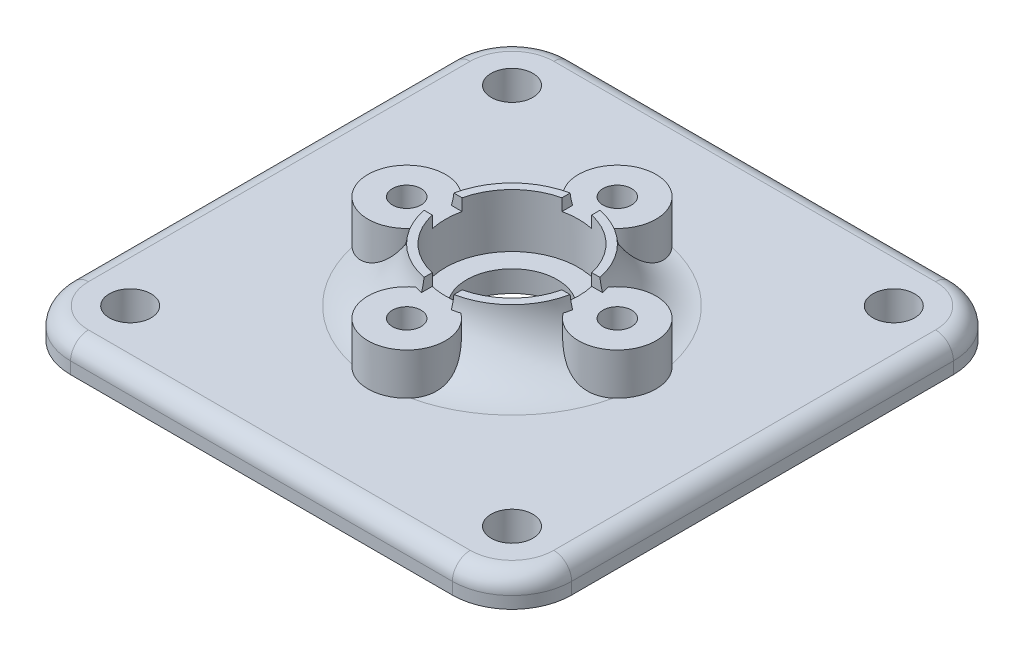
SolidWorks part; units mm, degrees
ref_plane "Front Plane" through (0, 0, 0) normal (0, 0, 1) x (1, 0, 0)
ref_plane "Top Plane" through (0, 0, 0) normal (0, 1, 0) x (1, 0, 0)
ref_plane "Right Plane" through (0, 0, 0) normal (1, 0, 0) x (0, 0, -1)
sketch "Sketch1" plane through (0, 0, 0) normal (0, 1, 0) x (1, 0, 0)
  line L1 (32, 42) -> (-32, 42)
  line L2 (42, 32) -> (42, -32)
  line L3 (32, -42) -> (-32, -42)
  line L4 (-42, 32) -> (-42, -32)
  line L5 (42, 42) -> (-42, -42) construction
  line L6 (42, -42) -> (-42, 42) construction
  arc A0 (32, 42) -> (42, 32) centre (32, 32) cw
  arc A1 (42, -32) -> (32, -42) centre (32, -32) cw
  arc A2 (-32, -42) -> (-42, -32) centre (-32, -32) cw
  arc A3 (-32, 42) -> (-42, 32) centre (-32, 32) ccw
  point P0 (0, 0)
  dimension "D1" = 10
  dimension "D2" = 84
extrude "Boss-Extrude1" add sketch "Sketch1" along normal blind 5 contours L1 A3 L4 A2 L3 A1 L2 A0
sketch "Sketch3" plane through (0, 0, 0) normal (0, 0, 1) x (1, 0, 0)
  line L0 (32, 5) -> (-32, 5) construction
  line L1 (0, 5) -> (-12.5, 5) construction
  line L3 (12.5, 14) -> (-12.5, 14) construction
  line L4 (-12.5, 5) -> (-12.5, 14)
  line L5 (-12.5, 5) -> (-11.15, 5)
  line L7 (-12.5, 14) -> (-11.15, 14)
  line L8 (-11.15, 14) -> (-11.15, 5)
  line L9 (-32, 5) -> (-12.5, 5)
  line L10 (0, 0) -> (0, -50000) construction
  line L11 (0, 5) -> (-9.6, 5)
  line L12 (0, 5) -> (0, 0)
  line L13 (-9.6, 5) -> (-9.6, 0)
  line L14 (32, 0) -> (-32, 0) construction
  line L15 (-9.6, 0) -> (0, 0)
  arc A3 (-9.6, 0) -> (-7.6, 5) centre (-7.3717, 2.0087) cw
  point P23 (0, 0)
  dimension "D8" = 3
  dimension "D1" = 12.5
  dimension "D2" = 9
  dimension "D3" = 11.15
  dimension "D5" = 9.6
  dimension "D9" = 2
revolve "Revolve2" add sketch "Sketch3" angle 360 about L10
revolve "Cut-Revolve2" cut sketch "Sketch3<5>" angle 360 about L10 region at (-4.7402, 2.4691, 0)
sketch "Sketch3<5>" plane through (0, 0, 0) normal (0, 0, 1) x (1, 0, 0) same geometry as "Sketch3"
sketch "Sketch19" plane through (0, 14, 0) normal (0, 1, 0) x (1, 0, 0)
  line L1 (15, 2.5) -> (-15, 2.5)
  line L2 (15, 2.5) -> (15, -2.5)
  line L3 (15, -2.5) -> (-15, -2.5)
  line L4 (-15, 2.5) -> (-15, -2.5)
  line L5 (15, 2.5) -> (-15, -2.5) construction
  line L6 (15, -2.5) -> (-15, 2.5) construction
  line L7 (-2.5, -15) -> (2.5, -15)
  line L8 (-2.5, -15) -> (-2.5, 15)
  line L9 (-2.5, 15) -> (2.5, 15)
  line L10 (2.5, -15) -> (2.5, 15)
  line L11 (-2.5, -15) -> (2.5, 15) construction
  line L12 (-2.5, 15) -> (2.5, -15) construction
  point P0 (0, 0)
  point P8 (0, 0)
  point P13 (2.7586, 5.6629)
  dimension "D1" = 5
  dimension "D2" = 30
extrude "Cut-Extrude1" cut sketch "Sketch19" against normal blind 2 contours L1 L4 L3 L2 | L8 L9 L10 L7
sketch "Sketch20" plane through (0, 5, 0) normal (0, 1, 0) x (1, 0, 0)
  line L0 (0, 0) -> (0, 17.65) construction
  line L1 (0, 0) -> (0, 17.65) construction
  line L2 (0, 0) -> (17.65, 0) construction
  circle A0 centre (0, 17.65) radius 6.5
  arc A1 (2.5, 10.8661) -> (-2.5, 10.8661) centre (0, 0) ccw construction
  circle A2 centre (17.65, 0) radius 6.5
  circle A3 centre (0, -17.65) radius 6.5
  circle A4 centre (-17.65, 0) radius 6.5
  point P4 (0, 0)
  point P8 (0, 0)
  dimension "D1" = 13
  dimension "D3" = 90
  dimension "D2" = 4
extrude "Boss-Extrude2" add sketch "Sketch20" along normal blind 7
sketch "Sketch23" plane through (0, 0, 0) normal (0, -1, 0) x (1, 0, 0)
  line L1 (-21.9, -2.4537) -> (-17.65, -4.9075)
  line L2 (-17.65, -4.9075) -> (-13.4, -2.4537)
  line L3 (-13.4, -2.4537) -> (-13.4, 2.4537)
  line L4 (-13.4, 2.4537) -> (-17.65, 4.9075)
  line L5 (-17.65, 4.9075) -> (-21.9, 2.4537)
  line L6 (-21.9, 2.4537) -> (-21.9, -2.4537)
  line L7 (-4.25, 15.1963) -> (0, 12.7425)
  line L8 (0, 12.7425) -> (4.25, 15.1963)
  line L9 (4.25, 15.1963) -> (4.25, 20.1037)
  line L10 (4.25, 20.1037) -> (0, 22.5575)
  line L11 (0, 22.5575) -> (-4.25, 20.1037)
  line L12 (-4.25, 20.1037) -> (-4.25, 15.1963)
  line L13 (17.65, -4.9075) -> (21.9, -2.4537)
  line L14 (21.9, -2.4537) -> (21.9, 2.4537)
  line L15 (21.9, 2.4537) -> (17.65, 4.9075)
  line L16 (17.65, 4.9075) -> (13.4, 2.4537)
  line L17 (13.4, 2.4537) -> (13.4, -2.4537)
  line L18 (13.4, -2.4537) -> (17.65, -4.9075)
  line L19 (-4.25, -20.1037) -> (0, -22.5575)
  line L20 (0, -22.5575) -> (4.25, -20.1037)
  line L21 (4.25, -20.1037) -> (4.25, -15.1963)
  line L22 (4.25, -15.1963) -> (0, -12.7425)
  line L23 (0, -12.7425) -> (-4.25, -15.1963)
  line L24 (-4.25, -15.1963) -> (-4.25, -20.1037)
  circle A0 centre (-17.65, 0) radius 4.25 construction
  circle A1 centre (0, 17.65) radius 4.25 construction
  circle A2 centre (17.65, 0) radius 4.25 construction
  circle A3 centre (0, -17.65) radius 4.25 construction
  dimension "D1" = 8.5
extrude "Cut-Extrude2" cut sketch "Sketch23" against normal blind 3.25
sketch "Sketch13" plane through (0, 5, 0) normal (0, 1, 0) x (1, 0, 0)
  line L1 (32, 32) -> (-32, 32) construction
  line L2 (32, 32) -> (32, -32) construction
  line L3 (32, -32) -> (-32, -32) construction
  line L4 (-32, 32) -> (-32, -32) construction
  line L5 (32, 32) -> (-32, -32) construction
  line L6 (32, -32) -> (-32, 32) construction
  point P0 (0, 0)
  dimension "D1" = 64
fillet "Fillet1" radius 3 8 edges at (42, 5, 0) (39.0711, 5, -39.0711) (0, 5, -42) (-39.0711, 5, -39.0711) (-42, 5, 0) (-39.0711, 5, 39.0711) (0, 5, 42) (39.0711, 5, 39.0711)
hole_wizard "M6 Clearance Hole1" positions "Sketch16" profile "Sketch18" hole size "M6" standard "ANSI Metric"
sketch "Sketch16" plane through (0, 5, 0) normal (0, 1, 0) x (1, 0, 0)
  point P0 (-32, 32)
  point P3 (-32, -32)
  point P6 (32, -32)
  point P9 (32, 32)
sketch "Sketch18" plane through (-32, 5, -32) normal (1, 0, 0) x (0, 0, 1)
  line L0 (0, 0) -> (0, 10.103)
  line L1 (0, 10.103) -> (3.5, 8)
  line L2 (3.5, 8) -> (3.5, 0)
  line L5 (3.5, 0) -> (0, 0)
  line L10 (0, 10.103) -> (-3.5, 8) construction
  line L11 (0, -6.35) -> (0, 107.95) construction
  dimension "Hole Dia." = 7
  dimension "Hole Depth" = 8
  dimension "Drill Angle" = 118
hole_wizard "M4 Clearance Hole1" positions "Sketch21" profile "Sketch22" hole size "M4" standard "ANSI Metric" end condition through all
sketch "Sketch21" plane through (0, 12, 0) normal (0, 1, 0) x (1, 0, 0)
  point P0 (-17.65, 0)
  point P3 (0, 17.65)
  point P6 (17.65, 0)
  point P9 (0, -17.65)
sketch "Sketch22" plane through (-17.65, 12, 0) normal (1, 0, 0) x (0, 0, 1)
  line L0 (0, 0) -> (0, 12)
  line L1 (0, 12) -> (2.4, 12)
  line L2 (2.4, 12) -> (2.4, 0)
  line L5 (2.4, 0) -> (0, 0)
  line L11 (0, -6.35) -> (0, 107.95) construction
  dimension "Thru Hole Dia." = 4.8
  dimension "Thru Hole Depth" = 12
fillet "Fillet2" radius 10 4 edges at (-8.8388, 5, 8.8388) (8.8388, 5, 8.8388) (8.8388, 5, -8.8388) (-8.8388, 5, -8.8388)
